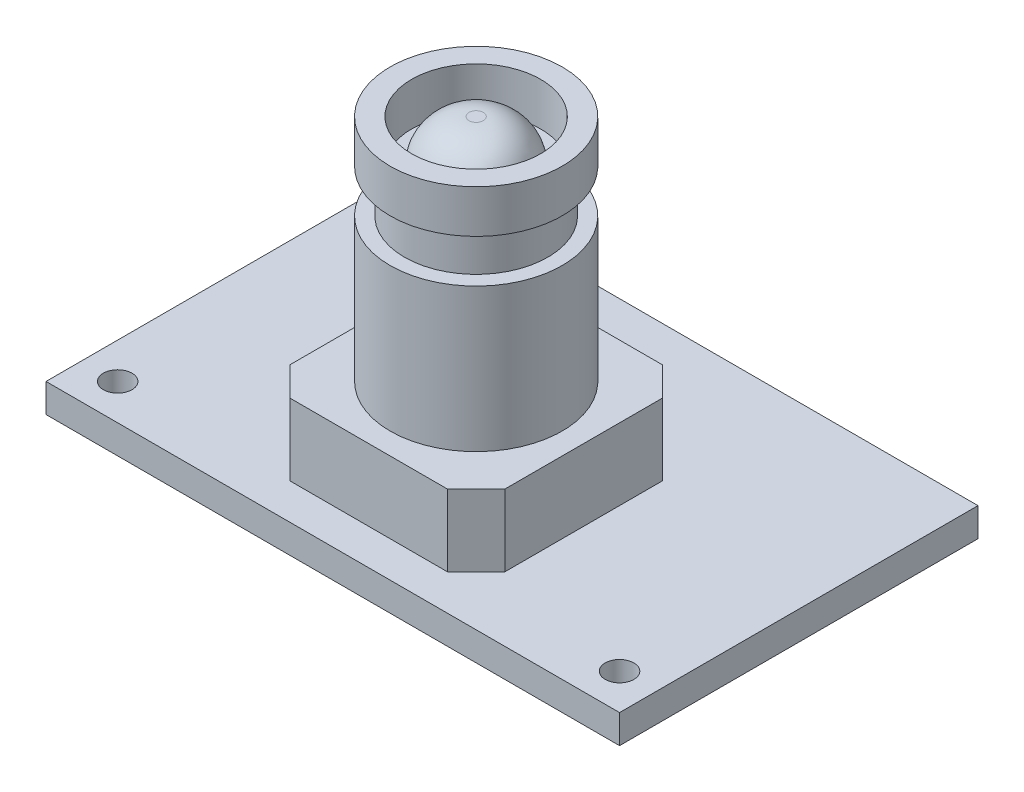
SolidWorks part; units mm, degrees
ref_plane "Face" through (0, 0, 0) normal (0, 0, 1) x (1, 0, 0)
ref_plane "Dessus" through (0, 0, 0) normal (0, 1, 0) x (1, 0, 0)
ref_plane "Droite" through (0, 0, 0) normal (1, 0, 0) x (0, 0, -1)
sketch "Esquisse1" plane through (0, 0, 0) normal (0, 1, 0) x (1, 0, 0)
  line L0 (0, 2.5) -> (40, 2.5) construction
  line L1 (0, 0) -> (40, 0)
  line L2 (0, 0) -> (0, 25)
  line L3 (0, 25) -> (40, 25)
  line L4 (40, 0) -> (40, 25)
  line L5 (20, 25) -> (20, 0) construction
  circle A0 centre (2.5, 2.5) radius 1
  circle A1 centre (37.5, 2.5) radius 1
  dimension "D3" = 2
  dimension "D1" = 40
  dimension "D2" = 25
  dimension "D4" = 2.5
  dimension "D5" = 2.5
extrude "Extrusion1" add sketch "Esquisse1" along normal blind 2
sketch "Esquisse2" plane through (0, 2, 0) normal (0, 1, 0) x (-1, 0, 0)
  line L0 (-20, -25) -> (-20, 0) construction
  line L1 (-40, -25) -> (0, -25) construction
  line L2 (0, 0) -> (-40, 0) construction
  line L3 (0, -10) -> (-40, -10) construction
  line L4 (-14.5, -17.5) -> (-25.5, -17.5)
  line L5 (-25.5, -17.5) -> (-27.5, -15.5)
  line L6 (-27.5, -15.5) -> (-27.5, -4.5)
  line L7 (-27.5, -4.5) -> (-25.5, -2.5)
  line L8 (-25.5, -2.5) -> (-14.5, -2.5)
  line L9 (-14.5, -2.5) -> (-12.5, -4.5)
  line L10 (-12.5, -4.5) -> (-12.5, -15.5)
  line L11 (-12.5, -15.5) -> (-14.5, -17.5)
  line L12 (-14.5, -17.5) -> (-14.5, -2.5) construction
  line L13 (-25.5, -17.5) -> (-25.5, -2.5) construction
  line L14 (-12.5, -15.5) -> (-27.5, -15.5) construction
  line L15 (-12.5, -4.5) -> (-27.5, -4.5) construction
  line L16 (-40, 0) -> (-40, -25) construction
  line L17 (0, -25) -> (0, 0) construction
  point P10 (-12.5, -10)
  point P17 (-27.5, -10)
  point P18 (-20, -17.5)
  point P19 (-20, -2.5)
  dimension "D1" = 15
  dimension "D2" = 15
  dimension "D3" = 45
  dimension "D4" = 11
  dimension "D5" = 10
extrude "Extrusion2" add sketch "Esquisse2" along normal blind 5
sketch "Esquisse3" plane through (0, 7, 0) normal (0, 1, 0) x (1, 0, 0)
  line L0 (20, 17.5) -> (20, 2.5) construction
  line L1 (25.5, 17.5) -> (14.5, 17.5) construction
  line L2 (14.5, 2.5) -> (25.5, 2.5) construction
  line L3 (12.5, 10) -> (27.5, 10) construction
  line L4 (12.5, 15.5) -> (12.5, 4.5) construction
  line L5 (27.5, 4.5) -> (27.5, 15.5) construction
  circle A0 centre (20, 10) radius 6
  dimension "D1" = 12
extrude "Extrusion3" add sketch "Esquisse3" along normal blind 10
sketch "Esquisse4" plane through (0, 17, 0) normal (0, 1, 0) x (1, 0, 0)
  circle A0 centre (20, 10) radius 5
  dimension "D1" = 10
extrude "Extrusion4" add sketch "Esquisse4" along normal blind 3
sketch "Esquisse5" plane through (0, 20, 0) normal (0, 1, 0) x (1, 0, 0)
  circle A0 centre (20, 10) radius 6
  circle A1 centre (20, 10) radius 6 construction
  circle A2 centre (20, 10) radius 4.5
  dimension "D1" = 9
extrude "Extrusion5" add sketch "Esquisse5" along normal blind 3
sketch "Esquisse6" plane through (0, 20, 0) normal (0, 1, 0) x (1, 0, 0)
  circle A0 centre (20, 10) radius 3.5
  dimension "D1" = 7
extrude "Extrusion6" add sketch "Esquisse6" along normal blind 3
fillet "Congé1" radius 3 1 edges at (20, 23, -6.5)
